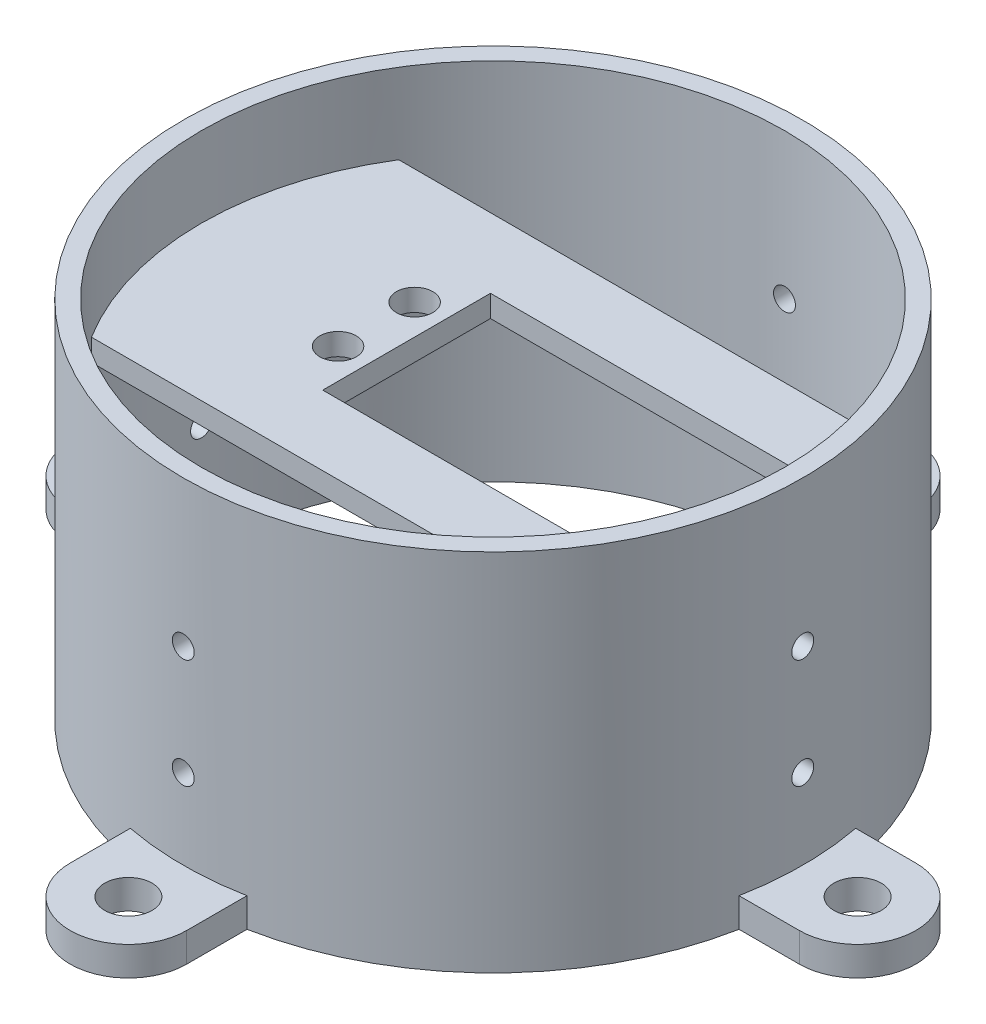
SolidWorks part; units mm, degrees
ref_plane "Front Plane" through (0, 0, 0) normal (0, 0, 1) x (1, 0, 0)
ref_plane "Top Plane" through (0, 0, 0) normal (0, 1, 0) x (1, 0, 0)
ref_plane "Right Plane" through (0, 0, 0) normal (1, 0, 0) x (0, 0, -1)
sketch "Sketch1" plane through (0, 0, 0) normal (0, 1, 0) x (1, 0, 0)
  circle A0 centre (0, 0) radius 40
  circle A1 centre (0, 0) radius 42.5
  dimension "D1" = 80
  dimension "D2" = 85
extrude "Boss-Extrude1" add sketch "Sketch1" along normal blind 50
sketch "Sketch2" plane through (0, 0, 0) normal (0, -1, 0) x (1, 0, 0)
  line L0 (42.5, 0) -> (50.0003, 0) construction
  line L1 (41.7403, 8) -> (50.0003, 8)
  line L2 (41.7403, -8) -> (50.0003, -8)
  circle A0 centre (0, 0) radius 42.5 construction
  circle A1 centre (50.0003, 0) radius 3.25
  arc A2 (50.0003, -8) -> (50.0003, 8) centre (50.0003, 0) ccw
  circle M3 centre (0, 0) radius 42.5
  dimension "D2" = 6.5
  dimension "D4" = 16
  dimension "D1" = 8.26
  dimension "D3" = 8
extrude "Boss-Extrude2" add sketch "Sketch2" against normal blind 4 contours L2 A2 L1 A1 M3 region at (45.8703, 0, 7.7719)
pattern_circular "CirPattern1" count 4 over 360 about axis through (0, 0, 0) along (0, 1, 0) of "Boss-Extrude2"
ref_plane "Plane1" through (0, 36, 0) normal (0, 1, 0) x (1, 0, 0)
sketch "Sketch4" plane through (0, 36, 0) normal (0, 1, 0) x (1, 0, 0)
  line L5 (34, -21.0713) -> (-34, -21.0713)
  line L7 (34, 21.0713) -> (-34, 21.0713)
  line L9 (34, -21.0713) -> (-34, 21.0713) construction
  line L10 (34, 21.0713) -> (-34, -21.0713) construction
  circle A3 centre (0, 0) radius 40 construction
  arc A4 (-34, 21.0713) -> (-34, -21.0713) centre (0, 0) ccw
  arc A5 (34, -21.0713) -> (34, 21.0713) centre (0, 0) ccw
  point P0 (0, 0)
  dimension "D1" = 68
extrude "Boss-Extrude3" add sketch "Sketch4" along normal blind 3
sketch "Sketch3" plane through (0, 39, 0) normal (0, 1, 0) x (1, 0, 0)
  line L0 (-15.9997, 5.25) -> (34.3003, 5.25) construction
  line L1 (-15.9997, 5.25) -> (-15.9997, -5.25) construction
  line L2 (-15.9997, -5.25) -> (34.3003, -5.25) construction
  line L3 (34.3003, 5.25) -> (34.3003, -5.25) construction
  line L4 (-15.9997, 5.25) -> (34.3003, -5.25) construction
  line L5 (34.3003, -5.25) -> (34.3003, 5.25) construction
  line L6 (34.3003, 5.25) -> (-15.9997, -5.25) construction
  line L7 (30.1503, -11.5) -> (-11.8497, -11.5)
  line L8 (30.1503, -11.5) -> (30.1503, 11.5)
  line L9 (30.1503, 11.5) -> (-11.8497, 11.5)
  line L10 (-11.8497, -11.5) -> (-11.8497, 11.5)
  line L11 (30.1503, -11.5) -> (-11.8497, 11.5) construction
  line L12 (30.1503, 11.5) -> (-11.8497, -11.5) construction
  line L13 (9.1503, 0) -> (50.0003, 0) construction
  circle A0 centre (34.3003, 5.25) radius 2.5
  circle A1 centre (34.3003, -5.25) radius 2.5
  circle A2 centre (-15.9997, -5.25) radius 2.5
  circle A3 centre (-15.9997, 5.25) radius 2.5
  circle A4 centre (9.1503, 0) radius 12.5 construction
  dimension "D1" = 5
  dimension "D4" = 25
  dimension "D2" = 10.5
  dimension "D3" = 50.3
  dimension "D5" = 42
  dimension "D6" = 23
  dimension "D7" = 40.85
extrude "Cut-Extrude1" cut sketch "Sketch3" against normal up to next
sketch "Sketch5" plane through (0, 0, 0) normal (0, 0, 1) x (1, 0, 0)
  line L0 (0, 0) -> (0, 36) construction
  line L1 (-60, 70) -> (40, 70)
  line L2 (-60, 70) -> (-60, 0)
  line L3 (-60, 0) -> (40, 0)
  line L4 (40, 70) -> (40, 0)
  line L5 (46.75, 36) -> (-46.75, 36) construction
  line L6 (-10, 0) -> (-10, 70) construction
  line L7 (8, 0) -> (41.7403, 0) construction
  circle A0 centre (-57, 67) radius 1.75
  circle A1 centre (35.33, 67) radius 1.75
  circle A2 centre (-57, 13.85) radius 1.75
  circle A3 centre (35.33, 13.85) radius 1.75
  dimension "D3" = 3.5
  dimension "D4" = 92.33
  dimension "D5" = 3
  dimension "D6" = 3
  dimension "D8" = 53.15
  dimension "D1" = 100
  dimension "D2" = 70
  dimension "D9" = 10
  dimension "D7" = 2
extrude "Boss-Extrude4" [suppressed] add sketch "Sketch5" along normal blind 2 from offset 42
fillet "Fillet1" [suppressed] radius 3
sketch "Sketch6" plane through (0, 0, 0) normal (0, 0, 1) x (1, 0, 0)
  line L0 (-41.7403, 0) -> (-8, 0) construction
  circle A0 centre (0, 15) radius 1.5
  circle A1 centre (0, 30) radius 1.5
  point P4 (0, 0)
  dimension "D1" = 15
  dimension "D2" = 3
  dimension "D3" = 15
extrude "Cut-Extrude2" cut sketch "Sketch6" against normal up to next and the other way up to next
pattern_circular "CirPattern2" count 2 over 90 about axis through (0, 50, 0) along (0, 1, 0) of "Cut-Extrude2"
